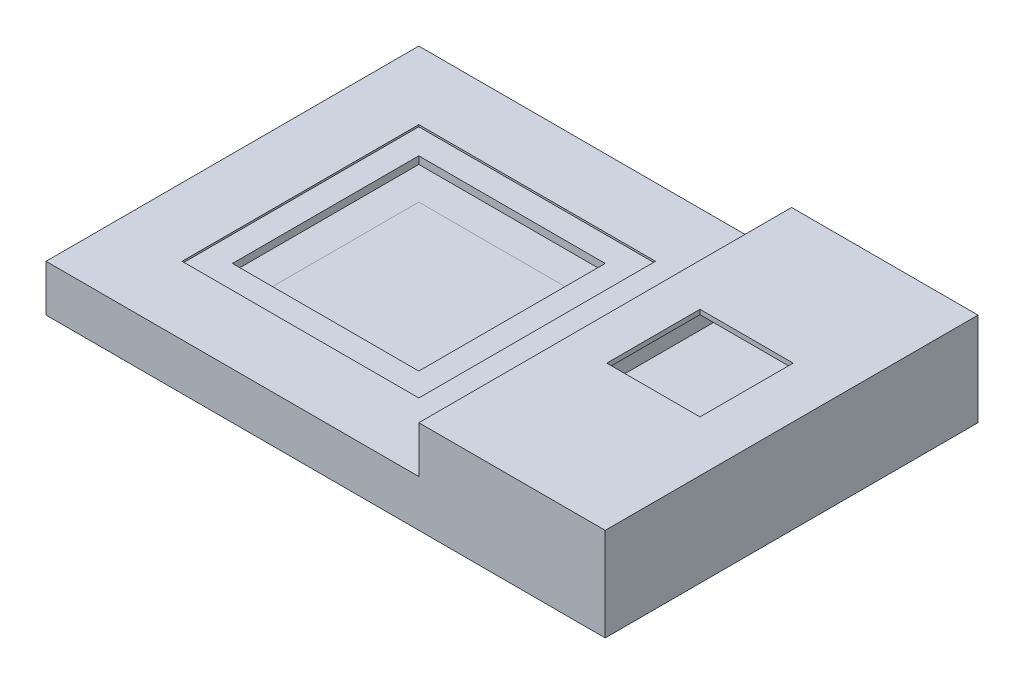
SolidWorks part; units mm, degrees
ref_plane "Front Plane" through (0, 0, 0) normal (0, 0, 1) x (1, 0, 0)
ref_plane "Top Plane" through (0, 0, 0) normal (0, 1, 0) x (1, 0, 0)
ref_plane "Right Plane" through (0, 0, 0) normal (1, 0, 0) x (0, 0, -1)
sketch "Sketch1" plane through (0, 0, 0) normal (0, 1, 0) x (1, 0, 0)
  line L1 (-20, -20) -> (20, -20)
  line L2 (-20, -20) -> (-20, 20)
  line L3 (-20, 20) -> (20, 20)
  line L4 (20, -20) -> (20, 20)
  line L5 (-20, -20) -> (20, 20) construction
  line L6 (-20, 20) -> (20, -20) construction
  line L7 (-10, -10) -> (10, -10)
  line L8 (-10, -10) -> (-10, 10)
  line L9 (-10, 10) -> (10, 10)
  line L10 (10, -10) -> (10, 10)
  line L11 (-10, -10) -> (10, 10) construction
  line L12 (-10, 10) -> (10, -10) construction
  line L13 (20, 20) -> (40, 20)
  line L14 (20, 20) -> (20, -20)
  line L15 (20, -20) -> (40, -20)
  line L16 (40, 20) -> (40, -20)
  point P0 (0, 0)
  point P6 (0, 0)
  point P13 (29.5459, 0.6229)
  dimension "D1" = 40
  dimension "D2" = 40
  dimension "D3" = 20
  dimension "D4" = 20
  dimension "D5" = 20
extrude "Boss-Extrude1" add sketch "Sketch1" against normal blind 5 contours L1 L4 L3 L2 L10 L7 L8 L9 region at (-19.4343, 0, 0)
extrude "Boss-Extrude2" add sketch "Sketch1<4>" against normal blind 5 and the other way blind 5 contours L13 L16 L15 L4
sketch "Sketch1<4>" plane through (0, 0, 0) normal (0, 1, 0) x (1, 0, 0) same geometry as "Sketch1"
sketch "Sketch2" plane through (0, 0, 0) normal (0, 1, 0) x (1, 0, 0)
  line L0 (-20, 20) -> (20, -20) construction
  line L1 (-12.7, 12.7) -> (12.7, 12.7)
  line L2 (-12.7, 12.7) -> (-12.7, -12.7)
  line L3 (-12.7, -12.7) -> (12.7, -12.7)
  line L4 (12.7, 12.7) -> (12.7, -12.7)
  point P6 (0, 0)
  point P7 (0, 0)
  point P8 (0, 0)
  point P9 (0, 0)
  dimension "D1" = 25.4
extrude "Cut-Extrude1" cut sketch "Sketch2" against normal blind 0.2
sketch "Sketch3" plane through (0, 0, 0) normal (0, 0, 1) x (1, 0, 0)
  line L0 (-20, -5) -> (-20, 0) construction
  line L1 (39.5, -1) -> (-19.5, -1)
  line L2 (39.5, -1) -> (39.5, -4.5)
  line L3 (39.5, -4.5) -> (-19.5, -4.5)
  line L4 (-19.5, -1) -> (-19.5, -4.5)
  line L5 (-20, 0) -> (20, 0) construction
  line L6 (-20, -5) -> (40, -5) construction
  line L7 (40, -5) -> (40, 5) construction
  dimension "D1" = 0.5
  dimension "D2" = 1
  dimension "D3" = 0.5
  dimension "D4" = 0.5
extrude "Cut-Extrude2" cut sketch "Sketch3" against normal blind 19.5 and the other way blind 19.5
sketch "Sketch4" plane through (0, 5, 0) normal (0, 1, 0) x (1, 0, 0)
  line L1 (24.5459, 5.6229) -> (34.5459, 5.6229)
  line L2 (24.5459, 5.6229) -> (24.5459, -4.3771)
  line L3 (24.5459, -4.3771) -> (34.5459, -4.3771)
  line L4 (34.5459, 5.6229) -> (34.5459, -4.3771)
  line L5 (24.5459, 5.6229) -> (34.5459, -4.3771) construction
  line L6 (24.5459, -4.3771) -> (34.5459, 5.6229) construction
  point P0 (29.5459, 0.6229)
  dimension "D1" = 10
  dimension "D2" = 10
sketch "Sketch5" plane through (0, 0, 0) normal (0, 0, 1) x (1, 0, 0)
  line L0 (20, 0) -> (40, 0) construction
  line L1 (39.5, -4.5) -> (20.5, -4.5)
  line L2 (39.5, -4.5) -> (39.5, 4.5)
  line L3 (39.5, 4.5) -> (20.5, 4.5)
  line L4 (20.5, 4.5) -> (20.5, -1)
  line L5 (39.5, -4.5) -> (20.5, 4.5) construction
  line L6 (39.5, 4.5) -> (20.5, -4.5) construction
  line L7 (20, 5) -> (40, 5) construction
  line L8 (40, 5) -> (40, -5) construction
  line L9 (20.5, -1) -> (20, -1)
  line L10 (20.5, -4.5) -> (20, -4.5)
  line L11 (-20, 0) -> (20, 0) construction
  line L12 (-20, -5) -> (40, -5) construction
  line L13 (20, -4.5) -> (20, -1)
  point P0 (30, 0)
  dimension "D1" = 0.5
  dimension "D2" = 0.5
  dimension "D3" = 1
  dimension "D5" = 0.5
extrude "Cut-Extrude3" cut sketch "Sketch5" against normal blind 19.5 and the other way blind 19.5
extrude "Cut-Extrude4" cut sketch "Sketch4" against normal blind 2
sketch "Sketch7" plane through (0, -4.5, 0) normal (0, 1, 0) x (1, 0, 0)
  line L1 (-10, -10) -> (10, -10)
  line L2 (-10, -10) -> (-10, 10)
  line L3 (-10, 10) -> (10, 10)
  line L4 (10, -10) -> (10, 10)
  line L5 (-10, -10) -> (10, 10) construction
  line L6 (-10, 10) -> (10, -10) construction
  point P0 (0, 0)
  point P7 (0, 0)
extrude "Boss-Extrude3" add sketch "Sketch7" against normal blind 0.5 separate body
